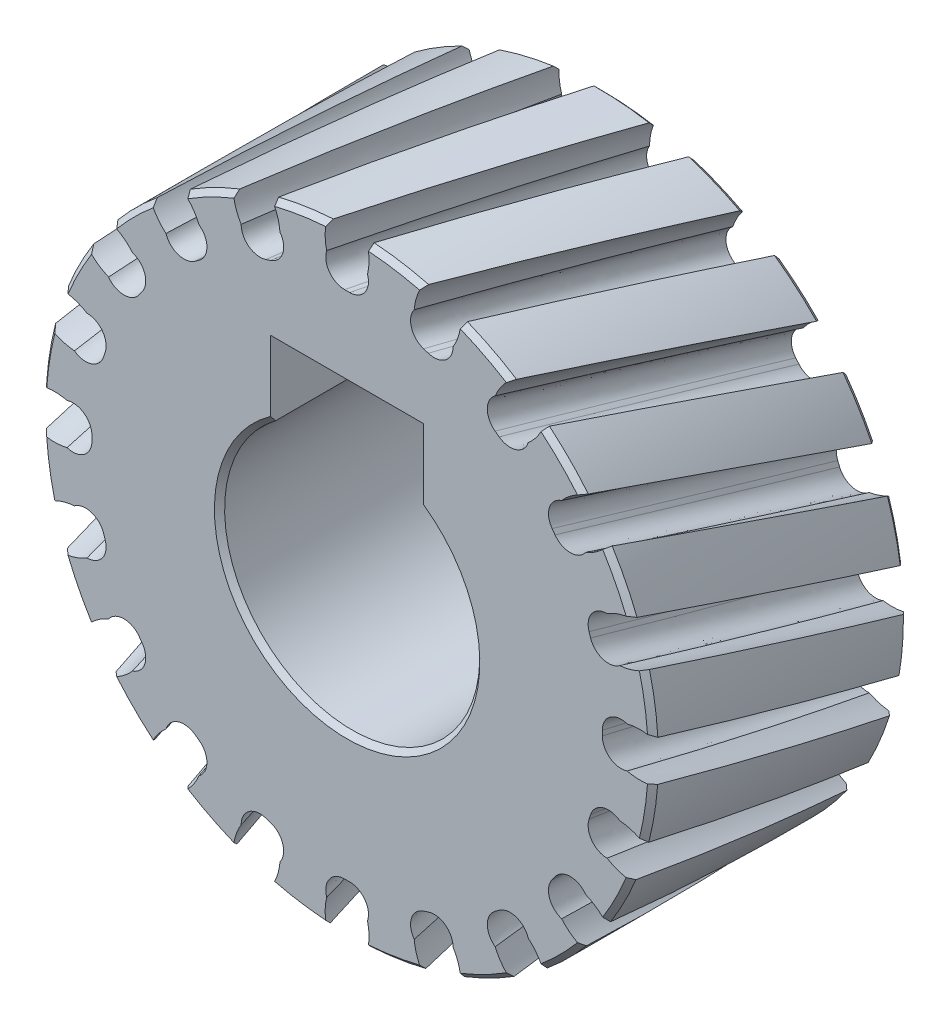
SolidWorks part; units mm, degrees
ref_plane "Front Plane" through (0, 0, 0) normal (0, 0, 1) x (1, 0, 0)
ref_plane "Top Plane" through (0, 0, 0) normal (0, 1, 0) x (1, 0, 0)
ref_plane "Right Plane" through (0, 0, 0) normal (1, 0, 0) x (0, 0, -1)
sketch "Sketch1" plane through (0, 0, 0) normal (0, 0, 1) x (1, 0, 0)
  line L2 (-74.8817, 16.2339) -> (-74.8817, 31.2339)
  line L3 (-74.8817, 31.2339) -> (-44.8817, 31.2339)
  line L4 (-44.8817, 16.2339) -> (-44.8817, 31.2339)
  circle A0 centre (-59.8817, -3.7661) radius 60
  arc A1 (-74.8817, 16.2339) -> (-44.8817, 16.2339) centre (-59.8817, -3.7661) ccw
  point P4 (-59.8817, 21.2339)
  dimension "D1" = 120
  dimension "D2" = 50
extrude "Boss-Extrude1" add sketch "Sketch1" along normal blind 25 and the other way blind 25
chamfer "Chamfer1" distance 1 angle 45 4 edges at (0.1183, -3.7661, -25) (-59.8817, -28.7661, -25) (0.1183, -3.7661, 25) (-59.8817, -28.7661, 25)
sketch "Sketch2" plane through (0, 0, 25) normal (0, 0, 1) x (1, 0, 0)
  circle A0 centre (-59.8817, -3.7661) radius 45
sketch "Sketch3" plane through (0, 0, 25) normal (0, 0, 1) x (1, 0, 0)
  circle A0 centre (-59.8817, -3.7661) radius 45
curve "Helix/Spiral2" pitch 1300 height 50 radius 45 centre (-59.8817, -3.7661, 25) axis (0, 0, -1) start towards (0, 1, 0)
sketch "Sketch4" plane through (0, 0, 25) normal (0, 0, 1) x (1, 0, 0)
  line L0 (-119.8817, -3.7661) -> (0.1183, -3.7661) construction
  line L1 (-59.8817, 56.2339) -> (-59.8817, -63.7661) construction
  line L2 (-59.8817, 56.2339) -> (-59.8817, 73.2246) construction
  line L3 (-60.3701, 46.2339) -> (-59.3933, 46.2339)
  circle A0 centre (-59.8817, -3.7661) radius 60 construction
  arc A1 (-55.8839, 56.1005) -> (-63.8795, 56.1005) centre (-59.8817, -3.7661) ccw
  circle A2 centre (-59.8817, -3.7661) radius 60 construction
  arc A3 (-63.8795, 56.1005) -> (-63.8795, 51.1005) centre (-53.5073, 53.6005) ccw
  arc A4 (-55.8839, 56.1005) -> (-55.8839, 51.1005) centre (-66.256, 53.6005) cw
  arc A5 (-63.8795, 51.1005) -> (-60.3701, 46.2339) centre (-60.3701, 49.9325) ccw
  arc A6 (-55.8839, 51.1005) -> (-59.3933, 46.2339) centre (-59.3933, 49.9325) cw
  point P19 (-59.8817, 46.2339)
  dimension "D1" = 4
  dimension "D2" = 7.9956
  dimension "D3" = 5
  dimension "D4" = 6
  dimension "D5" = 10
sweep "Cut-Sweep1" cut profiles "Sketch4" path "Helix/Spiral2"
pattern_circular "CirPattern1" count 20 over 360 about axis through (-59.8817, -3.7661, -25) along (0, 0, 1) of "Cut-Sweep1" reverse direction yes
